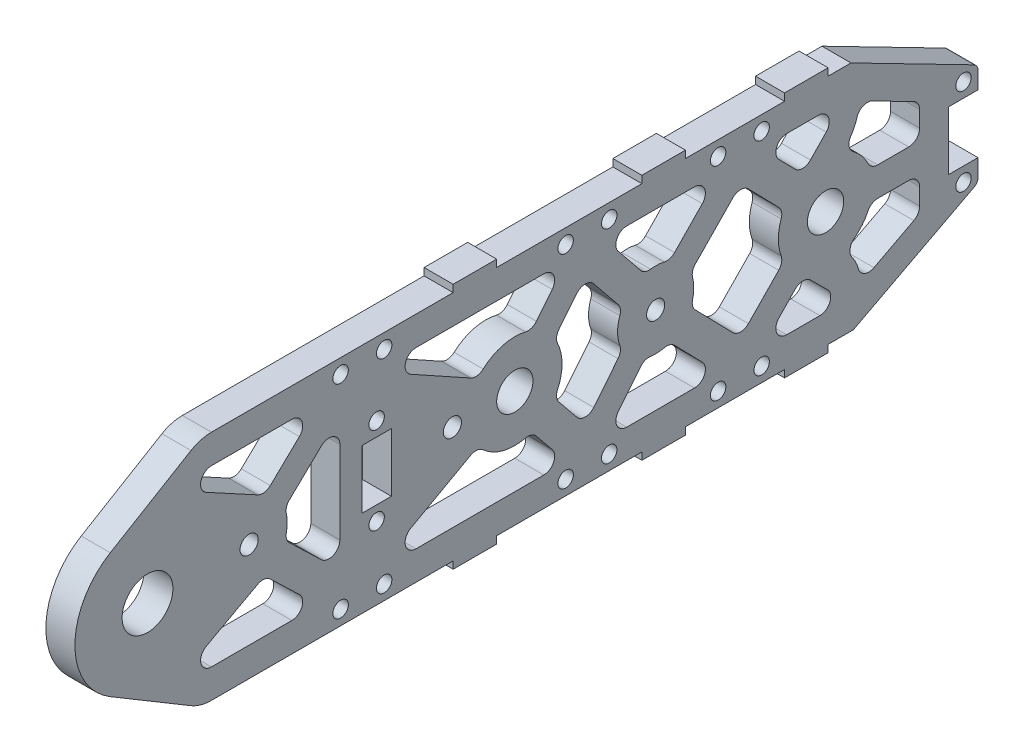
SolidWorks part; units mm, degrees
material "6061-T6 (SS)"
ref_plane "Front Plane" through (0, 0, 0) normal (0, 0, 1) x (1, 0, 0)
ref_plane "Top Plane" through (0, 0, 0) normal (0, 1, 0) x (1, 0, 0)
ref_plane "Right Plane" through (0, 0, 0) normal (1, 0, 0) x (0, 0, -1)
sketch "Sketch1" plane through (0, 0, 0) normal (1, 0, 0) x (0, 0, -1)
  line L0 (-160.655, 50.8) -> (93.345, 50.8)
  line L1 (93.345, 50.8) -> (93.345, -50.8)
  line L2 (93.345, -50.8) -> (-160.655, -50.8)
  line L3 (93.345, 0) -> (55.245, 50.8)
  line L4 (93.345, 0) -> (55.245, -50.8)
  circle A0 centre (0, 0) radius 38.1
  circle A1 centre (0, 0) radius 7.9375
  circle A2 centre (-38.1, 0) radius 7.9375
  circle A3 centre (-88.9, 0) radius 7.9375
  circle A4 centre (-88.9, 0) radius 39.751
  circle A5 centre (-38.1, 0) radius 25.4
  circle A6 centre (-160.655, 0) radius 11.1125
  circle A7 centre (-88.9, 0) radius 23.368
  circle A8 centre (-160.655, 0) radius 33.655
  circle A9 centre (-160.655, 0) radius 76.2
  circle A10 centre (-160.655, 0) radius 50.8
  dimension "D1" = 38.1
  dimension "D3" = 71.755
  dimension "D4" = 15.875
  dimension "D5" = 101.6
  dimension "D9" = 50.8
  dimension "D10" = 67.31
  dimension "D11" = 79.502
  dimension "D12" = 46.736
  dimension "D2" = 50.8
  dimension "D6" = 254
  dimension "D7" = 38.1
  dimension "D8" = 38.1
extrude "Boss-Extrude1" add sketch "Sketch1" along normal blind 12.7 contours A5 A0 A1 | A0 A5 | A10 A7 A9 A3 | A10 A7 A9 A4 | A7 A10 A4 | A7 A10 | A10 A4 A9 A7 | A9 A4 A5 A7 | A10 L2 A9 A4 | A4 A10 A8 | A8 A6 | A10 A4 A9 L0 | A9 A4 A5 A0 L2 L4 L3 L0 | A9 A3 A7 | A4 A5 | A0 A5 A4 A2 | A4 A8 | A0 A2 | A0 A2 | A3 A9 | A9 A3 region at (0, 24.069, -72.5203) region at (0, 42.9334, 118.4345) region at (0, 43.3242, 136.8815) region at (0, 26.7507, 103.5231) region at (0, 35.0406, 72.108) region at (0, -42.9334, 118.4345) region at (0, 0, 119.1262) region at (0, 24.4524, 42.4444) region at (0, 0, 55.9937) region at (0, 0, 97.9886) region at (0, 0, 76.9553) region at (0, -26.7507, 103.5231) region at (0, 0, 127.8393) region at (0, 0, 129.5966) region at (0, 0, 110.9718) region at (0, 0, 24.8917) region at (0, 34.9598, -12.3602) region at (0, 0, 90.0881) region at (0, 0, 83.0866) region at (0, 0, 34.5867) region at (0, 0, 41.3155)
sketch "Sketch2" plane through (12.7, 0, 0) normal (1, 0, 0) x (0, 0, -1)
  line L0 (-160.655, 50.8) -> (-211.455, 25.4)
  line L1 (-211.455, 25.4) -> (-211.455, -25.4)
  line L2 (-211.455, -25.4) -> (-160.655, -50.8)
  line L3 (-160.655, -50.8) -> (-160.655, -41.7462)
  line L4 (-160.655, -41.7462) -> (-204.0423, 0)
  line L5 (-204.0423, 0) -> (-160.655, 42.2841)
  line L6 (-160.655, 42.2841) -> (-160.655, 50.8)
extrude "Boss-Extrude2" add sketch "Sketch2" against normal blind 12.7
sketch "Sketch3" plane through (12.7, 0, 0) normal (1, 0, 0) x (0, 0, -1)
  line L0 (-211.455, 25.4) -> (-160.655, 50.8)
  line L1 (-160.655, 50.8) -> (-211.455, 50.8)
  line L2 (-211.455, 50.8) -> (-211.455, 25.4)
  line L3 (-211.455, -25.4) -> (-211.455, -50.8)
  line L4 (-211.455, -50.8) -> (-160.655, -50.8)
  line L5 (-160.655, -50.8) -> (-211.455, -25.4)
extrude "Cut-Extrude1" cut sketch "Sketch3" against normal through all
sketch "Sketch4" plane through (12.7, 0, 0) normal (1, 0, 0) x (0, 0, -1)
  line L0 (67.945, 33.8667) -> (67.945, -33.8667)
  line L1 (93.345, 0) -> (55.245, 50.8) construction
  line L2 (93.345, 0) -> (55.245, -50.8) construction
  line L3 (67.945, -33.8667) -> (93.345, 0)
  line L4 (93.345, 0) -> (67.945, 33.8667)
  dimension "D1" = 25.4
extrude "Cut-Extrude2" cut sketch "Sketch4" against normal through all
fillet "Fillet1" radius 25.4 4 edges at (6.35, -50.8, 160.655) (6.35, -25.4, 211.455) (6.35, 50.8, 160.655) (6.35, 25.4, 211.455)
mirror "Mirror1" about plane through (0, 33.8667, -67.945) normal (0, 0, 1) of "Cut-Extrude1", "Boss-Extrude2", "Boss-Extrude1"
sketch "Sketch5" plane through (12.7, 0, 0) normal (1, 0, 0) x (0, 0, -1)
  line L1 (55.245, 50.8) -> (80.645, 50.8)
  line L2 (55.245, 50.8) -> (55.245, -50.8)
  line L3 (55.245, -50.8) -> (80.645, -50.8)
  line L4 (80.645, 50.8) -> (80.645, -50.8)
extrude "Boss-Extrude3" add sketch "Sketch5" against normal up to surface (12.7 mm away) up to face at (0, 0, -127.9525)
sketch "Sketch6" plane through (12.7, 0, 0) normal (1, 0, 0) x (0, 0, -1)
  line L0 (-154.6589, 50.8) -> (296.545, 50.8) construction
  line L1 (202.565, 50.8) -> (347.345, 50.8)
  line L2 (202.565, 50.8) -> (202.565, -50.8)
  line L3 (202.565, -50.8) -> (347.345, -50.8)
  line L4 (347.345, 50.8) -> (347.345, -50.8)
  line L5 (347.345, 25.4) -> (347.345, -25.4) construction
extrude "Cut-Extrude3" cut sketch "Sketch6" against normal through all
sketch "Sketch7" plane through (0, 0, 0) normal (-1, 0, 0) x (0, 0, 1)
  line L0 (-151.765, 50.8) -> (-202.565, 25.4)
  line L1 (154.6589, 50.8) -> (-202.565, 50.8) construction
  line L2 (-202.565, 50.8) -> (-202.565, -50.8) construction
  line L3 (-202.565, 25.4) -> (-202.565, 50.8)
  line L4 (-202.565, 50.8) -> (-151.765, 50.8)
  line L5 (-151.765, 50.8) -> (-151.5363, 51.9987)
  line L6 (-151.765, -50.8) -> (-202.565, -25.4)
  line L7 (-202.565, -50.8) -> (154.6589, -50.8) construction
  line L8 (-202.565, -25.4) -> (-202.565, -50.8)
  line L9 (-202.565, -50.8) -> (-151.765, -50.8)
  line L10 (-347.345, -25.4) -> (-202.565, -25.4) construction
  line L11 (-202.565, 25.4) -> (-347.345, 25.4) construction
  line L12 (-347.345, 25.4) -> (-296.545, 50.8) construction
  line L13 (-296.545, -50.8) -> (-347.345, -25.4) construction
  line M2 (154.6589, 50.8) -> (-202.565, 50.8)
  line M3 (-202.565, 50.8) -> (-202.565, -50.8)
  line M4 (-202.565, -50.8) -> (154.6589, -50.8)
extrude "Cut-Extrude4" cut sketch "Sketch7" against normal through all contours L0 M2 M3 | L6 M4 M3 region at (0, -42.3333, -185.6317) region at (0, 42.3333, -185.6317)
sketch "Sketch8" plane through (0, 0, 0) normal (-1, 0, 0) x (0, 0, 1)
  line L0 (-202.565, 25.4) -> (-151.765, 50.8)
  line L1 (-151.765, 50.8) -> (-147.0197, 50.8)
  line L2 (154.6589, 50.8) -> (-151.765, 50.8) construction
  line L3 (160.655, 50.8) -> (-296.545, 50.8) construction
  line L4 (-147.0197, 50.8) -> (-202.565, 22.283)
  line L5 (-202.565, 25.4) -> (-202.565, -25.4) construction
  line L6 (-350.2961, 22.283) -> (-163.3958, 22.283) construction
  line L7 (-202.565, 22.283) -> (-202.565, 25.4)
  line L8 (-202.565, -22.283) -> (-148.0573, -50.8)
  line L9 (-163.3958, -22.283) -> (-350.2961, -22.283) construction
  line L10 (-151.765, -50.8) -> (154.6589, -50.8) construction
  line L11 (-159.9149, -25.9312) -> (-147.2469, -52.4995) construction
  line L12 (-148.0573, -50.8) -> (-151.765, -50.8)
  line L13 (-151.765, -50.8) -> (-202.565, -25.4)
  line L14 (-202.565, -25.4) -> (-202.565, -22.283)
extrude "Cut-Extrude5" cut sketch "Sketch8" against normal through all
sketch "Sketch10" plane through (12.7, 0, 0) normal (1, 0, 0) x (0, 0, -1)
  line L0 (202.565, 22.283) -> (202.565, -22.283) construction
  line L1 (202.565, 12.827) -> (189.738, 12.827)
  line L2 (202.565, 12.827) -> (202.565, -12.827)
  line L3 (202.565, -12.827) -> (189.738, -12.827)
  line L4 (189.738, 12.827) -> (189.738, -12.827)
  line L5 (-53.975, 0) -> (0, 0) construction
  line L6 (-66.929, 12.827) -> (-53.975, 12.827)
  line L7 (-66.929, 12.827) -> (-66.929, -12.827)
  line L8 (-66.929, -12.827) -> (-53.975, -12.827)
  line L9 (-53.975, 12.827) -> (-53.975, -12.827)
  line L10 (0, 0) -> (189.738, 0) construction
  line L11 (-60.452, 12.827) -> (-60.452, -12.827) construction
  circle A0 centre (0, 0) radius 7.9375 construction
  dimension "D1" = 12.827
  dimension "D2" = 25.654
  dimension "D3" = 60.452
  dimension "D4" = 12.954
extrude "Cut-Extrude6" cut sketch "Sketch10" against normal through all
hole_wizard "1/4 Clearance Hole1" positions "Sketch12" profile "Sketch11" hole size "1/4" standard "ANSI Inch"
sketch "Sketch12" plane through (12.7, 0, 0) normal (1, 0, 0) x (0, 0, -1)
  line L0 (-60.452, 19.05) -> (-60.452, 12.827) construction
  line L1 (-53.975, 12.827) -> (-66.929, 12.827) construction
  line L2 (-60.452, 12.827) -> (-60.452, -12.827) construction
  line L3 (-66.929, -12.827) -> (-53.975, -12.827) construction
  line L4 (-60.452, -12.827) -> (-60.452, -19.05) construction
  line L5 (-60.452, -19.05) -> (196.215, -19.05) construction
  line L6 (196.215, -19.05) -> (196.215, 19.05) construction
  line L7 (196.215, 19.05) -> (-60.452, 19.05) construction
  line L9 (202.565, 22.283) -> (202.565, 12.827) construction
  point P0 (-60.452, 19.05)
  point P2 (-60.452, -19.05)
  point P4 (196.215, -19.05)
  point P6 (196.215, 19.05)
  dimension "D1" = 6.35
  dimension "D2" = 38.1
sketch "Sketch11" plane through (12.7, 19.05, 60.452) normal (0, 1, 0) x (0, 0, -1)
  line L0 (0, 0) -> (0, 14.7298)
  line L1 (0, 14.7298) -> (3.3782, 12.7)
  line L2 (3.3782, 12.7) -> (3.3782, 0)
  line L5 (3.3782, 0) -> (0, 0)
  line L10 (0, 14.7298) -> (-3.3782, 12.7) construction
  line L11 (0, -6.35) -> (0, 107.95) construction
  dimension "Hole Dia." = 6.7564
  dimension "Hole Depth" = 12.7
  dimension "Drill Angle" = 118
hole_wizard "3/8-16 Tapped Hole1" positions "Sketch15" profile "Sketch14" tap size "3/8-16" standard "ANSI Inch"
sketch "Sketch15" plane through (12.7, 0, 0) normal (1, 0, 0) x (0, 0, -1)
  line L0 (-160.655, 0) -> (189.738, 0) construction
  line L1 (189.738, 12.827) -> (189.738, -12.827) construction
  line L2 (-116.205, 31.75) -> (-27.305, 31.75) construction
  line L3 (-27.305, 31.75) -> (61.595, 31.75) construction
  circle A0 centre (-27.305, 0) radius 31.75
  circle A1 centre (61.595, 0) radius 31.75
  circle A2 centre (-116.205, 0) radius 31.75
  point P8 (-116.205, 0)
  point P10 (-27.305, 0)
  point P12 (61.595, 0)
  dimension "D1" = 63.5
  dimension "D2" = 88.9
  dimension "D3" = 44.45
sketch "Sketch14" plane through (12.7, 0, 116.205) normal (0, 1, 0) x (0, 0, -1)
  line L0 (0, 0) -> (0, 26.2607)
  line L1 (0, 26.2607) -> (3.9687, 23.876)
  line L2 (3.9687, 23.876) -> (3.9687, 0)
  line L5 (3.9687, 0) -> (0, 0)
  line L10 (0, 26.2607) -> (-3.9688, 23.876) construction
  line L11 (0, -6.35) -> (0, 107.95) construction
  dimension "Tap Drill Dia." = 7.9375
  dimension "Tap Drill Depth" = 23.876
  dimension "Drill Angle" = 118
sketch "Sketch16" plane through (12.7, 0, 0) normal (1, 0, 0) x (0, 0, -1)
  line L12 (-148.5978, 36.5604) -> (-108.2499, 14.648)
  line L13 (-148.5978, -36.5604) -> (-108.2499, -14.648)
  line L14 (-76.5302, 19.05) -> (-76.5302, -19.05)
  line L15 (-116.205, 0) -> (135.89, 0)
  line L16 (143.95, 38.1) -> (121.0311, 14.322)
  line L17 (144.9358, -38.1) -> (121.3379, -14.6336)
  line L18 (-76.5302, 19.05) -> (-76.5302, 38.1)
  line L19 (-76.5302, -19.05) -> (-76.5302, -38.1)
  line L20 (-116.205, 0) -> (-76.5302, -38.1)
  line L21 (-116.205, 0) -> (-76.5302, 38.1)
  line L22 (-107.0373, 0) -> (-72.1319, -33.5199)
  line L23 (-107.0373, 0) -> (-72.1319, 33.5199)
  line L24 (177.038, -21.305) -> (177.038, 21.1126)
  line L25 (177.038, 21.1126) -> (143.95, 38.1)
  line L26 (143.95, 38.1) -> (-154.6589, 38.1)
  line L27 (-160.3385, 36.7592) -> (-191.7346, 21.0612)
  line L28 (-198.755, 9.7019) -> (-198.755, -9.7019)
  line L29 (-191.7346, -21.0612) -> (-160.3385, -36.7592)
  line L30 (-154.6589, -38.1) -> (144.9358, -38.1)
  line L31 (144.9358, -38.1) -> (177.038, -21.305)
  line L32 (177.038, -21.305) -> (177.038, 21.1126)
  line L33 (177.038, 21.1126) -> (143.95, 38.1)
  line L34 (143.95, 38.1) -> (-154.6589, 38.1)
  line L35 (-160.3385, 36.7592) -> (-191.7346, 21.0612)
  line L36 (-198.755, 9.7019) -> (-198.755, -9.7019)
  line L37 (-191.7346, -21.0612) -> (-160.3385, -36.7592)
  line L38 (-154.6589, -38.1) -> (144.9358, -38.1)
  line L39 (144.9358, -38.1) -> (177.038, -21.305)
  line L40 (-125.3727, 0) -> (-80.9285, -42.6801)
  line L41 (-125.3727, 0) -> (-80.9285, 42.6801)
  line L42 (135.89, 0) -> (98.7425, 38.1)
  line L43 (135.89, 0) -> (98.7425, -38.1)
  line L44 (98.7425, -38.1) -> (61.595, 0)
  line L45 (61.595, 0) -> (98.7425, 38.1)
  line L46 (98.7425, 38.1) -> (98.7425, -38.1) construction
  line L47 (0, 0) -> (30.7975, 38.1)
  line L48 (30.7975, 38.1) -> (61.595, 0)
  line L49 (61.595, 0) -> (30.7975, -38.1)
  line L50 (30.7975, -38.1) -> (0, 0)
  line L51 (30.7975, 38.1) -> (30.7975, -38.1) construction
  line L52 (70.4637, 0) -> (98.7425, 29.0039)
  line L53 (127.0213, 0) -> (98.7425, 29.0039)
  line L54 (127.0213, 0) -> (98.7425, -29.0039)
  line L55 (98.7425, -29.0039) -> (70.4637, 0)
  line L56 (52.7263, 0) -> (98.7425, 47.1961)
  line L57 (144.7587, 0) -> (98.7425, 47.1961)
  line L58 (144.7587, 0) -> (98.7425, -47.1961)
  line L59 (98.7425, -47.1961) -> (52.7263, 0)
  line L60 (30.7975, 27.9988) -> (53.4299, 0)
  line L61 (53.4299, 0) -> (30.7975, -27.9988)
  line L62 (30.7975, -27.9988) -> (8.1651, 0)
  line L63 (8.1651, 0) -> (30.7975, 27.9988)
  line L64 (30.7975, 48.2012) -> (69.7601, 0)
  line L65 (69.7601, 0) -> (30.7975, -48.2012)
  line L66 (30.7975, -48.2012) -> (-8.1651, 0)
  line L67 (-8.1651, 0) -> (30.7975, 48.2012)
  line L68 (-19.2235, 14.5786) -> (-52.6568, 33.1121)
  line L69 (-52.6568, 33.1121) -> (-61.6546, 38.1)
  line L70 (-19.2235, -14.5786) -> (-52.6568, -33.1121)
  line L71 (-52.6568, -33.1121) -> (-61.6546, -38.1)
  circle A6 centre (-160.655, 0) radius 23.8125
  circle A7 centre (-160.655, 0) radius 23.8125
  arc A8 (-154.6589, 38.1) -> (-160.3385, 36.7592) centre (-154.6589, 25.4) ccw
  arc A9 (-191.7346, 21.0612) -> (-198.755, 9.7019) centre (-186.055, 9.7019) ccw
  arc A10 (-198.755, -9.7019) -> (-191.7346, -21.0612) centre (-186.055, -9.7019) ccw
  arc A11 (-160.3385, -36.7592) -> (-154.6589, -38.1) centre (-154.6589, -25.4) ccw
  arc A12 (-154.6589, 38.1) -> (-160.3385, 36.7592) centre (-154.6589, 25.4) ccw
  arc A13 (-191.7346, 21.0612) -> (-198.755, 9.7019) centre (-186.055, 9.7019) ccw
  arc A14 (-198.755, -9.7019) -> (-191.7346, -21.0612) centre (-186.055, -9.7019) ccw
  arc A15 (-160.3385, -36.7592) -> (-154.6589, -38.1) centre (-154.6589, -25.4) ccw
  circle A17 centre (-27.305, 0) radius 16.6687
  circle A18 centre (-27.305, 0) radius 16.6687
  circle A20 centre (-116.205, 0) radius 16.6687
  circle A21 centre (-116.205, 0) radius 16.6687
  circle A23 centre (-60.452, 19.05) radius 16.0782
  circle A24 centre (-60.452, 19.05) radius 16.0782
  circle A26 centre (-60.452, -19.05) radius 16.0782
  circle A27 centre (-60.452, -19.05) radius 16.0782
  circle A29 centre (0, 0) radius 20.6375
  circle A30 centre (0, 0) radius 20.6375
  circle A32 centre (61.595, 0) radius 16.6687
  circle A33 centre (61.595, 0) radius 16.6687
  circle A34 centre (-154.6589, 25.4) radius 12.7
  circle A35 centre (135.89, 0) radius 20.6375
  circle A36 centre (135.89, 0) radius 20.6375
  circle A37 centre (-154.6589, -25.4) radius 12.7
  dimension "D10" = 6.35
  dimension "D12" = 6.35
  dimension "D1" = 12.7
  dimension "D2" = 12.7
  dimension "D3" = 12.7
  dimension "D4" = 12.7
  dimension "D5" = 12.7
  dimension "D6" = 12.7
  dimension "D7" = 12.7
  dimension "D8" = 12.7
  dimension "D9" = 12.7
  dimension "D11" = 6.35
  dimension "D13" = 6.35
  dimension "D14" = 6.35
  dimension "D15" = 6.35
extrude "Cut-Extrude7" cut sketch "Sketch16" against normal through all contours A34 L12 L41 L34 | A37 L38 L40 L13 | A21 L15 L14 L18 L23 | A21 L22 L19 L14 L15 | A30 L67 L34 L69 L68 A18 | A30 A18 L70 L71 L38 L66 | A33 L15 A30 L62 L61 | A33 L60 L63 A30 L15 | A33 L65 L38 L59 | A33 L56 L34 L64 | A36 L53 L52 A33 L15 | A36 L15 A33 L55 L54 | L17 L58 L38 | L57 L16 L34 region at (12.7, 30.5071, 115.5656) region at (12.7, 10.2026, 85.8113) region at (12.7, -30.5071, 115.5656) region at (12.7, 29.438, 15.7525) region at (12.7, -10.2026, 85.8113) region at (12.7, -29.438, 15.7525) region at (12.7, 29.4455, -63.7069) region at (12.7, 10.599, -31.7998) region at (12.7, -10.599, -31.7998) region at (12.7, -29.4455, -63.7069) region at (12.7, 31.8526, -125.8154) region at (12.7, 10.4699, -97.8767) region at (12.7, -10.4699, -97.8767) region at (12.7, -31.8183, -126.1774)
fillet "Fillet2" radius 4.7625 44 edges at (6.35, -19.255, -125.9851) (6.35, -38.1, -144.9358) (6.35, -38.1, -107.6112) (6.35, 38.1, -143.95) (6.35, 19.3577, -125.8849) (6.35, 38.1, -107.6112) (6.35, -9.6267, -117.6353) (6.35, -29.0039, -98.7425) (6.35, 6.6019, -76.9006) (6.35, 29.0039, -98.7425) (6.35, 9.6267, -117.6353) (6.35, -6.6019, -76.9006) (6.35, -15.4678, -67.8074) (6.35, -38.1, -89.8738) (6.35, -15.9776, -56.8449) (6.35, -38.1, -38.9626) (6.35, 15.9776, -56.8449) (6.35, 38.1, -89.8738) (6.35, 15.4678, -67.8074) (6.35, 38.1, -38.9626) (6.35, -7.9939, -46.9681) (6.35, -27.9988, -30.7975) (6.35, 11.2792, -17.2825) (6.35, 27.9988, -30.7975) (6.35, 7.9939, -46.9681) (6.35, -11.2792, -17.2825) (6.35, -19.2629, -7.4058) (6.35, -38.1, -22.6324) (6.35, -12.5752, 16.3637) (6.35, -38.1, 61.6546) (6.35, 12.5752, 16.3637) (6.35, 38.1, -22.6324) (6.35, 19.2629, -7.4058) (6.35, 38.1, 61.6546) (6.35, -15.2965, 109.444) (6.35, -38.1, 85.6979) (6.35, -38.1, 154.6589) (6.35, 29.2962, 76.5302) (6.35, -29.2962, 76.5302) (6.35, -6.0949, 100.6905) (6.35, 6.0949, 100.6905) (6.35, 38.1, 85.6979) (6.35, 15.2965, 109.444) (6.35, 38.1, 154.6589)
sketch "Sketch17" plane through (12.7, 0, 0) normal (1, 0, 0) x (0, 0, -1)
  line L0 (-176.9295, 27.2617) -> (-141.6354, 48.3314)
  line L1 (-141.6354, -48.3314) -> (-176.9295, -27.2617)
  line L2 (148.0573, -50.8) -> (-154.6589, -50.8) construction
  line L3 (-154.6589, 50.8) -> (147.0197, 50.8) construction
  line L4 (-132.6844, 50.8) -> (-211.455, 50.8)
  line L5 (-211.455, 50.8) -> (-211.455, -50.8)
  line L6 (-211.455, -50.8) -> (-132.6844, -50.8)
  circle A0 centre (-160.655, 0) radius 31.75
  circle A1 centre (-132.6844, 33.3375) radius 17.4625
  circle A2 centre (-132.6844, -33.3375) radius 17.4625
  dimension "D1" = 63.5
extrude "Cut-Extrude8" cut sketch "Sketch17" against normal through all contours A2 L1 A0 L0 A1 L4 L5 L6 region at (12.7, 0, 193.6906)
fillet "Fillet3" radius 3.175 2 edges at (6.35, -22.283, -202.565) (6.35, 22.283, -202.565)
hole_wizard "1/4 Clearance Hole2" positions "Sketch19" profile "Sketch18" hole size "1/4" standard "ANSI Inch" end condition through all
sketch "Sketch19" plane through (12.7, 0, 0) normal (1, 0, 0) x (0, 0, -1)
  line L0 (-148.1372, 44.45) -> (159.3881, 44.45) construction
  line L1 (-176.9295, 27.2617) -> (-141.6354, 48.3314) construction
  line L2 (200.8401, 23.1685) -> (147.0197, 50.8) construction
  line L4 (-132.6844, 50.8) -> (147.0197, 50.8) construction
  point P10 (-76.2, 44.45)
  point P12 (-57.15, 44.45)
  point P14 (22.225, 44.45)
  point P16 (41.275, 44.45)
  point P18 (88.9, 44.45)
  point P20 (107.95, 44.45)
  dimension "D1" = 6.35
  dimension "D2" = 19.05
  dimension "D3" = 19.05
  dimension "D4" = 19.05
  dimension "D5" = 57.15
  dimension "D6" = 22.225
  dimension "D7" = 88.9
sketch "Sketch18" plane through (12.7, 44.45, 76.2) normal (0, 1, 0) x (0, 0, -1)
  line L0 (0, 0) -> (0, 12.7)
  line L1 (0, 12.7) -> (3.3782, 12.7)
  line L2 (3.3782, 12.7) -> (3.3782, 0)
  line L5 (3.3782, 0) -> (0, 0)
  line L11 (0, -6.35) -> (0, 107.95) construction
  dimension "Thru Hole Dia." = 6.7564
  dimension "Thru Hole Depth" = 12.7
sketch "Sketch20" plane through (12.7, 0, 0) normal (1, 0, 0) x (0, 0, -1)
  line L0 (-132.6844, 50.8) -> (147.0197, 50.8) construction
  line L1 (-26.9875, 50.8) -> (-7.9375, 50.8)
  line L2 (-26.9875, 50.8) -> (-26.9875, 53.975)
  line L3 (-26.9875, 53.975) -> (-7.9375, 53.975)
  line L4 (-7.9375, 50.8) -> (-7.9375, 53.975)
  line L5 (127.4848, 50.8) -> (127.4848, -50.8) construction
  line L6 (55.5625, 50.8) -> (74.6125, 50.8)
  line L7 (55.5625, 50.8) -> (55.5625, 53.975)
  line L8 (55.5625, 53.975) -> (74.6125, 53.975)
  line L9 (74.6125, 50.8) -> (74.6125, 53.975)
  line L10 (137.0098, 50.8) -> (117.9598, 50.8)
  line L11 (137.0098, 50.8) -> (137.0098, 53.975)
  line L12 (137.0098, 53.975) -> (117.9598, 53.975)
  line L13 (117.9598, 50.8) -> (117.9598, 53.975)
  line L14 (148.0573, -50.8) -> (-132.6844, -50.8) construction
  line L15 (127.4848, -50.8) -> (65.0875, 50.8) construction
  line L16 (65.0875, 50.8) -> (65.0875, -50.8) construction
  line L17 (65.0875, -50.8) -> (-17.4625, 50.8) construction
  line L18 (-17.4625, 50.8) -> (-17.4625, -50.8) construction
  line L19 (-57.15, 44.45) -> (-17.4625, 44.45) construction
  line L20 (-17.4625, 44.45) -> (22.225, 44.45) construction
  line L21 (22.225, 44.45) -> (41.275, 44.45) construction
  line L22 (41.275, 44.45) -> (65.0875, 44.45) construction
  line L23 (65.0875, 44.45) -> (88.9, 44.45) construction
  line L24 (88.9, 44.45) -> (107.95, 44.45) construction
  line L25 (107.95, 44.45) -> (127.4848, 44.45) construction
  line L26 (127.4848, 44.45) -> (147.0197, 44.45) construction
  line L27 (147.0197, 44.45) -> (147.0197, 50.8) construction
  dimension "D1" = 19.05
  dimension "D2" = 3.175
extrude "Boss-Extrude4" add sketch "Sketch20" against normal up to surface (12.7 mm away) up to face at (0, 44.45, 72.8218)
mirror "Mirror3" about plane through (0, 0, 0) normal (0, 1, 0) of "Boss-Extrude4", "1/4 Clearance Hole2"
sketch "Sketch21" plane through (12.7, 0, 0) normal (1, 0, 0) x (0, 0, -1)
  line L56 (138.4382, 14.0813) -> (145.3178, 21.2189)
  line L57 (138.4382, 14.0813) -> (145.3178, 21.2189)
  line L58 (135.89, 0) -> (189.738, 0)
  line L59 (145.7058, -20.9552) -> (138.3507, -13.6411)
  line L60 (145.7058, -20.9552) -> (138.3507, -13.6411)
  line L61 (144.9358, -38.1) -> (137.0098, -38.1)
  line L62 (137.0098, 38.1) -> (143.95, 38.1)
  line L63 (177.038, -21.305) -> (144.9358, -38.1)
  line L64 (177.038, 21.1126) -> (177.038, -21.305)
  line L65 (143.95, 38.1) -> (177.038, 21.1126)
  line L66 (144.9358, -38.1) -> (137.0098, -38.1)
  line L67 (137.0098, 38.1) -> (143.95, 38.1)
  line L68 (177.038, -21.305) -> (144.9358, -38.1)
  line L69 (177.038, 21.1126) -> (177.038, -21.305)
  line L70 (143.95, 38.1) -> (177.038, 21.1126)
  line L71 (189.738, 12.827) -> (189.738, -12.827) construction
  line L72 (135.89, -6.35) -> (189.738, -6.35)
  line L73 (135.89, 6.35) -> (189.738, 6.35)
  circle A0 centre (135.89, 0) radius 20.6375
  arc A20 (113.3621, 14.0094) -> (138.4382, 14.0813) centre (125.8653, 26.2) ccw
  arc A21 (145.3178, 21.2189) -> (132.7449, 50.8) centre (132.7449, 33.3375) ccw
  arc A23 (145.3178, 21.2189) -> (132.7449, 50.8) centre (132.7449, 33.3375) ccw
  arc A25 (133.3925, -50.8) -> (145.7058, -20.9552) centre (133.3925, -33.3375) ccw
  arc A26 (133.3925, -50.8) -> (145.7058, -20.9552) centre (133.3925, -33.3375) ccw
  dimension "D1" = 12.7
  dimension "D4" = 6.35
  dimension "D2" = 12.7
  dimension "D3" = 12.7
  dimension "D5" = 6.35
extrude "Cut-Extrude9" cut sketch "Sketch21" against normal through all contours A23 L57 A0 L73 L69 L70 | A26 L68 L69 L72 A0 L60 region at (12.7, 18.1688, -161.6433) region at (12.7, -18.1719, -161.8706)
fillet "Fillet4" radius 4.7625 10 edges at (6.35, -19.061, -143.801) (6.35, -6.35, -177.038) (6.35, -21.305, -177.038) (6.35, -35.0471, -150.7711) (6.35, -6.35, -155.5263) (6.35, 21.1126, -177.038) (6.35, 6.35, -177.038) (6.35, 6.35, -155.5263) (6.35, 19.2244, -143.3954) (6.35, 34.9245, -150.1352)
